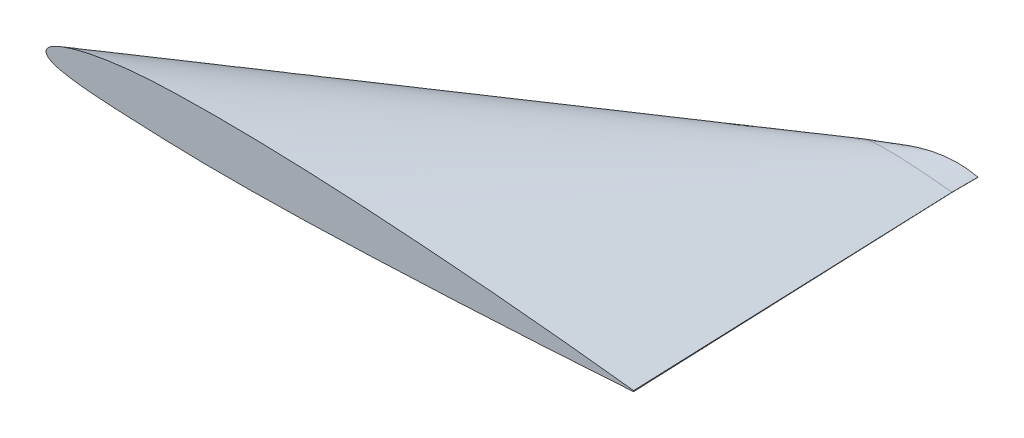
SolidWorks part; units mm, degrees
ref_plane "Plan de face" through (0, 0, 0) normal (0, 0, 1) x (1, 0, 0)
ref_plane "Plan de dessus" through (0, 0, 0) normal (0, 1, 0) x (1, 0, 0)
ref_plane "Plan de droite" through (0, 0, 0) normal (1, 0, 0) x (0, 0, -1)
curve "Courbe1"
  spline degree 3 poles (1018.0214, 0.8551, 0) (1017.4995, 0.9169, 0) (1015.4153, 1.1635, 0) (1010.7382, 1.7165, 0) (1002.9747, 2.6279, 0) (992.1722, 3.8816, 0) (978.3961, 5.4547, 0) (961.7307, 7.3239, 0) (942.2774, 9.4592, 0) (920.1552, 11.8271, 0) (895.4991, 14.3917, 0) (868.4602, 17.118, 0) (839.2041, 19.9687, 0) (807.9105, 22.9034, 0) (774.7711, 25.8837, 0) (739.9899, 28.8733, 0) (703.7802, 31.83, 0) (666.3653, 34.7159, 0) (627.9753, 37.4876, 0) (588.8466, 40.1073, 0) (549.2206, 42.5324, 0) (509.3421, 44.7223, 0) (469.4571, 46.6336, 0) (429.8121, 48.2309, 0) (390.6523, 49.4751, 0) (352.2202, 50.3347, 0) (314.754, 50.7806, 0) (278.4854, 50.792, 0) (243.6395, 50.3489, 0) (210.2839, 49.4637, 0) (178.6046, 48.0469, 0) (148.8474, 45.6903, 0) (121.3708, 42.6096, 0) (96.3889, 38.903, 0) (74.057, 34.7027, 0) (54.5094, 30.1347, 0) (37.8533, 25.3237, 0) (24.1753, 20.3842, 0) (13.4966, 15.4299, 0) (5.8515, 10.4906, 0) (0.9704, 5.571, 0) (-0.6493, -0.0648, 0) (2.0456, -5.2599, 0) (7.7408, -9.1365, 0) (16.0826, -12.5545, 0) (27.3008, -15.5285, 0) (41.3409, -18.1297, 0) (58.1495, -20.3675, 0) (77.6199, -22.2824, 0) (99.6342, -23.9255, 0) (124.0585, -25.3476, 0) (150.7475, -26.6259, 0) (179.5838, -27.8076, 0) (210.5631, -29.0818, 0) (243.5406, -30.0321, 0) (278.2985, -30.5898, 0) (314.476, -30.7851, 0) (351.8516, -30.6369, 0) (390.1961, -30.1714, 0) (429.2739, -29.4218, 0) (468.8455, -28.4222, 0) (508.668, -27.2083, 0) (548.4968, -25.815, 0) (588.0867, -24.2794, 0) (627.1936, -22.6305, 0) (665.5767, -20.9028, 0) (702.9992, -19.1236, 0) (739.2307, -17.3199, 0) (774.0468, -15.514, 0) (807.2325, -13.7303, 0) (838.582, -11.9881, 0) (867.9013, -10.3078, 0) (895.0089, -8.7106, 0) (919.7362, -7.2128, 0) (941.9306, -5.8374, 0) (961.4532, -4.5978, 0) (978.1828, -3.5146, 0) (992.0153, -2.6055, 0) (1002.8642, -1.879, 0) (1010.6624, -1.354, 0) (1015.3606, -1.033, 0) (1017.4544, -0.8907, 0) (1017.9786, -0.8551, 0) knots 0 0 0 0 0.000766 0.003061 0.006869 0.012167 0.018922 0.027092 0.036626 0.047465 0.059542 0.072781 0.087102 0.102414 0.118624 0.135631 0.15333 0.171611 0.190362 0.209467 0.228808 0.248265 0.267718 0.287047 0.306134 0.324861 0.343113 0.360781 0.377757 0.393939 0.409446 0.424002 0.437467 0.449765 0.460829 0.4706 0.479033 0.486099 0.491795 0.49616 0.499335 0.50173 0.504125 0.507289 0.511617 0.517238 0.524181 0.532434 0.541962 0.552713 0.564629 0.577644 0.591683 0.606723 0.622865 0.639799 0.657423 0.67563 0.694311 0.713352 0.732636 0.752045 0.77146 0.790762 0.80983 0.828548 0.8468 0.864473 0.881458 0.897648 0.912944 0.927252 0.940481 0.952549 0.963383 0.972913 0.981081 0.987834 0.993132 0.996939 0.999234 1 1 1 1
sketch "Esquisse1" plane through (0, 0, 0) normal (0, 0, 1) x (1, 0, 0)
  line L0 (1018.0214, 0.8551) -> (1017.9786, -0.8551)
  spline S0 degree 3 poles (2019.3627, 1669.0879) (1545.321, -65.0784) (1279.5358, -30.0658) (1010.7382, 1.7165) (1002.9747, 2.6279) (992.1722, 3.8816) (978.3961, 5.4547) (961.7307, 7.3239) (942.2774, 9.4592) (920.1552, 11.8271) (895.4991, 14.3917) (868.4602, 17.118) (839.2041, 19.9687) (807.9105, 22.9034) (774.7711, 25.8837) (739.9899, 28.8733) (703.7802, 31.83) (666.3653, 34.7159) (627.9753, 37.4876) (588.8466, 40.1073) (549.2206, 42.5324) (509.3421, 44.7223) (469.4571, 46.6336) (429.8121, 48.2309) (390.6523, 49.4751) (352.2202, 50.3347) (314.754, 50.7806) (278.4854, 50.792) (243.6395, 50.3489) (210.2839, 49.4637) (178.6046, 48.0469) (148.8474, 45.6903) (121.3708, 42.6096) (96.3889, 38.903) (74.057, 34.7027) (54.5094, 30.1347) (37.8533, 25.3237) (24.1753, 20.3842) (13.4966, 15.4299) (5.8515, 10.4906) (0.9704, 5.571) (-0.6493, -0.0648) (2.0456, -5.2599) (7.7408, -9.1365) (16.0826, -12.5545) (27.3008, -15.5285) (41.3409, -18.1297) (58.1495, -20.3675) (77.6199, -22.2824) (99.6342, -23.9255) (124.0585, -25.3476) (150.7475, -26.6259) (179.5838, -27.8076) (210.5631, -29.0818) (243.5406, -30.0321) (278.2985, -30.5898) (314.476, -30.7851) (351.8516, -30.6369) (390.1961, -30.1714) (429.2739, -29.4218) (468.8455, -28.4222) (508.668, -27.2083) (548.4968, -25.815) (588.0867, -24.2794) (627.1936, -22.6305) (665.5767, -20.9028) (702.9992, -19.1236) (739.2307, -17.3199) (774.0468, -15.514) (807.2325, -13.7303) (838.582, -11.9881) (867.9013, -10.3078) (895.0089, -8.7106) (919.7362, -7.2128) (941.9306, -5.8374) (961.4532, -4.5978) (978.1828, -3.5146) (992.0153, -2.6055) (1002.8642, -1.879) (1010.6624, -1.354) (1187.4361, 10.7265) (1362.009, 16.688) (1404.8675, 1937.5859) knots -0.387905 -0.387905 -0.387905 -0.387905 0.000766 0.003061 0.006869 0.012167 0.018922 0.027092 0.036626 0.047465 0.059542 0.072781 0.087102 0.102414 0.118624 0.135631 0.15333 0.171611 0.190362 0.209467 0.228808 0.248265 0.267718 0.287047 0.306134 0.324861 0.343113 0.360781 0.377757 0.393939 0.409446 0.424002 0.437467 0.449765 0.460829 0.4706 0.479033 0.486099 0.491795 0.49616 0.499335 0.50173 0.504125 0.507289 0.511617 0.517238 0.524181 0.532434 0.541962 0.552713 0.564629 0.577644 0.591683 0.606723 0.622865 0.639799 0.657423 0.67563 0.694311 0.713352 0.732636 0.752045 0.77146 0.790762 0.80983 0.828548 0.8468 0.864473 0.881458 0.897648 0.912944 0.927252 0.940481 0.952549 0.963383 0.972913 0.981081 0.987834 0.993132 0.996939 0.999234 1.251559 1.251559 1.251559 1.251559 only from (1018.0214, 0.8551) to (1017.9786, -0.8551) construction
  spline S1 degree 3 poles (1018.0214, 0.8551) (1015.9372, 1.1018) (1011.2602, 1.6553) (1002.9747, 2.6279) (992.1722, 3.8816) (978.3961, 5.4547) (961.7307, 7.3239) (942.2774, 9.4592) (920.1552, 11.8271) (895.4991, 14.3917) (868.4602, 17.118) (839.2041, 19.9687) (807.9105, 22.9034) (774.7711, 25.8837) (739.9899, 28.8733) (703.7802, 31.83) (666.3653, 34.7159) (627.9753, 37.4876) (588.8466, 40.1073) (549.2206, 42.5324) (509.3421, 44.7223) (469.4571, 46.6336) (429.8121, 48.2309) (390.6523, 49.4751) (352.2202, 50.3347) (314.754, 50.7806) (278.4854, 50.792) (243.6395, 50.3489) (210.2839, 49.4637) (178.6046, 48.0469) (148.8474, 45.6903) (121.3708, 42.6096) (96.3889, 38.903) (74.057, 34.7027) (54.5094, 30.1347) (37.8533, 25.3237) (24.1753, 20.3842) (13.4966, 15.4299) (5.8515, 10.4906) (0.9704, 5.571) (-0.6493, -0.0648) (2.0456, -5.2599) (7.7408, -9.1365) (16.0826, -12.5545) (27.3008, -15.5285) (41.3409, -18.1297) (58.1495, -20.3675) (77.6199, -22.2824) (99.6342, -23.9255) (124.0585, -25.3476) (150.7475, -26.6259) (179.5838, -27.8076) (210.5631, -29.0818) (243.5406, -30.0321) (278.2985, -30.5898) (314.476, -30.7851) (351.8516, -30.6369) (390.1961, -30.1714) (429.2739, -29.4218) (468.8455, -28.4222) (508.668, -27.2083) (548.4968, -25.815) (588.0867, -24.2794) (627.1936, -22.6305) (665.5767, -20.9028) (702.9992, -19.1236) (739.2307, -17.3199) (774.0468, -15.514) (807.2325, -13.7303) (838.582, -11.9881) (867.9013, -10.3078) (895.0089, -8.7106) (919.7362, -7.2128) (941.9306, -5.8374) (961.4532, -4.5978) (978.1828, -3.5146) (992.0153, -2.6055) (1002.8642, -1.879) (1010.6624, -1.354) (1015.3606, -1.033) (1017.4544, -0.8907) (1017.9786, -0.8551) knots 0 0 0 0 0.003061 0.006869 0.012167 0.018922 0.027092 0.036626 0.047465 0.059542 0.072781 0.087102 0.102414 0.118624 0.135631 0.15333 0.171611 0.190362 0.209467 0.228808 0.248265 0.267718 0.287047 0.306134 0.324861 0.343113 0.360781 0.377757 0.393939 0.409446 0.424002 0.437467 0.449765 0.460829 0.4706 0.479033 0.486099 0.491795 0.49616 0.499335 0.50173 0.504125 0.507289 0.511617 0.517238 0.524181 0.532434 0.541962 0.552713 0.564629 0.577644 0.591683 0.606723 0.622865 0.639799 0.657423 0.67563 0.694311 0.713352 0.732636 0.752045 0.77146 0.790762 0.80983 0.828548 0.8468 0.864473 0.881458 0.897648 0.912944 0.927252 0.940481 0.952549 0.963383 0.972913 0.981081 0.987834 0.993132 0.996939 0.999234 1 1 1 1
ref_plane "Plan1" through (0, 0, 3692) normal (0, 0, 1) x (1, 0, 0)
curve "Courbe6"
  spline degree 3 poles (1163.1375, 5.4995, 3692) (1159.7811, 5.8967, 3692) (1146.3774, 7.4829, 3692) (1116.2978, 11.0395, 3692) (1066.3687, 16.9004, 3692) (996.8956, 24.9635, 3692) (908.2981, 35.0805, 3692) (801.1189, 47.1015, 3692) (676.0101, 60.8344, 3692) (533.737, 76.0629, 3692) (375.1675, 92.5562, 3692) (201.2738, 110.0899, 3692) (13.1209, 128.4236, 3692) (-188.1357, 147.2973, 3692) (-401.2627, 166.4645, 3692) (-624.9492, 185.6913, 3692) (-857.8221, 204.7062, 3692) (-1098.4462, 223.2663, 3692) (-1345.3414, 241.0915, 3692) (-1596.9874, 257.9399, 3692) (-1851.8314, 273.5362, 3692) (-2108.3, 287.6194, 3692) (-2364.8099, 299.9116, 3692) (-2619.7762, 310.1846, 3692) (-2871.6223, 318.1858, 3692) (-3118.7881, 323.7144, 3692) (-3359.7421, 326.5819, 3692) (-3592.9943, 326.6555, 3692) (-3817.0964, 323.8061, 3692) (-4031.6141, 318.1125, 3692) (-4235.3513, 309.001, 3692) (-4426.7271, 293.8451, 3692) (-4603.4357, 274.0325, 3692) (-4764.1004, 250.1942, 3692) (-4907.7217, 223.1815, 3692) (-5033.4374, 193.8031, 3692) (-5140.5567, 162.863, 3692) (-5228.523, 131.0958, 3692) (-5297.1999, 99.2336, 3692) (-5346.3678, 67.4673, 3692) (-5377.759, 35.8287, 3692) (-5388.1761, -0.4169, 3692) (-5370.8441, -33.8274, 3692) (-5334.217, -58.7592, 3692) (-5280.5689, -80.741, 3692) (-5208.4223, -99.8674, 3692) (-5118.1271, -116.5961, 3692) (-5010.0265, -130.9881, 3692) (-4884.8083, -143.3033, 3692) (-4743.2287, -153.8705, 3692) (-4586.1505, -163.0167, 3692) (-4414.5067, -171.2373, 3692) (-4229.054, -178.8373, 3692) (-4029.8189, -187.0319, 3692) (-3817.7327, -193.1434, 3692) (-3594.1965, -196.7305, 3692) (-3361.5299, -197.9864, 3692) (-3121.1589, -197.0334, 3692) (-2874.556, -194.0395, 3692) (-2623.2373, -189.2185, 3692) (-2368.743, -182.7897, 3692) (-2112.6351, -174.9833, 3692) (-1856.4867, -166.0227, 3692) (-1601.8747, -156.1465, 3692) (-1350.369, -145.5422, 3692) (-1103.5178, -134.4311, 3692) (-862.8449, -122.9884, 3692) (-629.8315, -111.3885, 3692) (-405.9209, -99.7741, 3692) (-192.4958, -88.3026, 3692) (9.1204, -77.0986, 3692) (197.6796, -66.2922, 3692) (372.0148, -56.0201, 3692) (531.0422, -46.3873, 3692) (673.7795, -37.5414, 3692) (799.3341, -29.5694, 3692) (906.9261, -22.6031, 3692) (995.8864, -16.7568, 3692) (1065.6581, -12.0843, 3692) (1115.8103, -8.708, 3692) (1146.0257, -6.6432, 3692) (1159.4908, -5.7285, 3692) (1162.8625, -5.4995, 3692) knots 0 0 0 0 0.000766 0.003061 0.006869 0.012167 0.018922 0.027092 0.036626 0.047465 0.059542 0.072781 0.087102 0.102414 0.118624 0.135631 0.15333 0.171611 0.190362 0.209467 0.228808 0.248265 0.267718 0.287047 0.306134 0.324861 0.343113 0.360781 0.377757 0.393939 0.409446 0.424002 0.437467 0.449765 0.460829 0.4706 0.479033 0.486099 0.491795 0.49616 0.499335 0.50173 0.504125 0.507289 0.511617 0.517238 0.524181 0.532434 0.541962 0.552713 0.564629 0.577644 0.591683 0.606723 0.622865 0.639799 0.657423 0.67563 0.694311 0.713352 0.732636 0.752045 0.77146 0.790762 0.80983 0.828548 0.8468 0.864473 0.881458 0.897648 0.912944 0.927252 0.940481 0.952549 0.963383 0.972913 0.981081 0.987834 0.993132 0.996939 0.999234 1 1 1 1
sketch "Esquisse4" plane through (0, 0, 3692) normal (0, 0, 1) x (1, 0, 0)
  line L0 (1163.1375, 5.4995) -> (1162.8625, -5.4995)
  spline S0 degree 3 poles (3092.3515, 339.1342) (2401.749, -144.1196) (1767.5466, -65.9634) (1116.2978, 11.0395) (1066.3687, 16.9004) (996.8956, 24.9635) (908.2981, 35.0805) (801.1189, 47.1015) (676.0101, 60.8344) (533.737, 76.0629) (375.1675, 92.5562) (201.2738, 110.0899) (13.1209, 128.4236) (-188.1357, 147.2973) (-401.2627, 166.4645) (-624.9492, 185.6913) (-857.8221, 204.7062) (-1098.4462, 223.2663) (-1345.3414, 241.0915) (-1596.9874, 257.9399) (-1851.8314, 273.5362) (-2108.3, 287.6194) (-2364.8099, 299.9116) (-2619.7762, 310.1846) (-2871.6223, 318.1858) (-3118.7881, 323.7144) (-3359.7421, 326.5819) (-3592.9943, 326.6555) (-3817.0964, 323.8061) (-4031.6141, 318.1125) (-4235.3513, 309.001) (-4426.7271, 293.8451) (-4603.4357, 274.0325) (-4764.1004, 250.1942) (-4907.7217, 223.1815) (-5033.4374, 193.8031) (-5140.5567, 162.863) (-5228.523, 131.0958) (-5297.1999, 99.2336) (-5346.3678, 67.4673) (-5377.759, 35.8287) (-5388.1761, -0.4169) (-5370.8441, -33.8274) (-5334.217, -58.7592) (-5280.5689, -80.741) (-5208.4223, -99.8674) (-5118.1271, -116.5961) (-5010.0265, -130.9881) (-4884.8083, -143.3033) (-4743.2287, -153.8705) (-4586.1505, -163.0167) (-4414.5067, -171.2373) (-4229.054, -178.8373) (-4029.8189, -187.0319) (-3817.7327, -193.1434) (-3594.1965, -196.7305) (-3361.5299, -197.9864) (-3121.1589, -197.0334) (-2874.556, -194.0395) (-2623.2373, -189.2185) (-2368.743, -182.7897) (-2112.6351, -174.9833) (-1856.4867, -166.0227) (-1601.8747, -156.1465) (-1350.369, -145.5422) (-1103.5178, -134.4311) (-862.8449, -122.9884) (-629.8315, -111.3885) (-405.9209, -99.7741) (-192.4958, -88.3026) (9.1204, -77.0986) (197.6796, -66.2922) (372.0148, -56.0201) (531.0422, -46.3873) (673.7795, -37.5414) (799.3341, -29.5694) (906.9261, -22.6031) (995.8864, -16.7568) (1065.6581, -12.0843) (1115.8103, -8.708) (1645.6756, 27.5023) (2159.3351, 54.5502) (2585.29, 1222.9368) knots -0.141853 -0.141853 -0.141853 -0.141853 0.000766 0.003061 0.006869 0.012167 0.018922 0.027092 0.036626 0.047465 0.059542 0.072781 0.087102 0.102414 0.118624 0.135631 0.15333 0.171611 0.190362 0.209467 0.228808 0.248265 0.267718 0.287047 0.306134 0.324861 0.343113 0.360781 0.377757 0.393939 0.409446 0.424002 0.437467 0.449765 0.460829 0.4706 0.479033 0.486099 0.491795 0.49616 0.499335 0.50173 0.504125 0.507289 0.511617 0.517238 0.524181 0.532434 0.541962 0.552713 0.564629 0.577644 0.591683 0.606723 0.622865 0.639799 0.657423 0.67563 0.694311 0.713352 0.732636 0.752045 0.77146 0.790762 0.80983 0.828548 0.8468 0.864473 0.881458 0.897648 0.912944 0.927252 0.940481 0.952549 0.963383 0.972913 0.981081 0.987834 0.993132 0.996939 0.999234 1.113577 1.113577 1.113577 1.113577 only from (1163.1375, 5.4995) to (1162.8625, -5.4995) construction
  spline S1 degree 3 poles (1163.1375, 5.4995) (1159.7811, 5.8967) (1146.3774, 7.4829) (1116.2978, 11.0395) (1066.3687, 16.9004) (996.8956, 24.9635) (908.2981, 35.0805) (801.1189, 47.1015) (676.0101, 60.8344) (533.737, 76.0629) (375.1675, 92.5562) (201.2738, 110.0899) (13.1209, 128.4236) (-188.1357, 147.2973) (-401.2627, 166.4645) (-624.9492, 185.6913) (-857.8221, 204.7062) (-1098.4462, 223.2663) (-1345.3414, 241.0915) (-1596.9874, 257.9399) (-1851.8314, 273.5362) (-2108.3, 287.6194) (-2364.8099, 299.9116) (-2619.7762, 310.1846) (-2871.6223, 318.1858) (-3118.7881, 323.7144) (-3359.7421, 326.5819) (-3592.9943, 326.6555) (-3817.0964, 323.8061) (-4031.6141, 318.1125) (-4235.3513, 309.001) (-4426.7271, 293.8451) (-4603.4357, 274.0325) (-4764.1004, 250.1942) (-4907.7217, 223.1815) (-5033.4374, 193.8031) (-5140.5567, 162.863) (-5228.523, 131.0958) (-5297.1999, 99.2336) (-5346.3678, 67.4673) (-5377.759, 35.8287) (-5388.1761, -0.4169) (-5370.8441, -33.8274) (-5334.217, -58.7592) (-5280.5689, -80.741) (-5208.4223, -99.8674) (-5118.1271, -116.5961) (-5010.0265, -130.9881) (-4884.8083, -143.3033) (-4743.2287, -153.8705) (-4586.1505, -163.0167) (-4414.5067, -171.2373) (-4229.054, -178.8373) (-4029.8189, -187.0319) (-3817.7327, -193.1434) (-3594.1965, -196.7305) (-3361.5299, -197.9864) (-3121.1589, -197.0334) (-2874.556, -194.0395) (-2623.2373, -189.2185) (-2368.743, -182.7897) (-2112.6351, -174.9833) (-1856.4867, -166.0227) (-1601.8747, -156.1465) (-1350.369, -145.5422) (-1103.5178, -134.4311) (-862.8449, -122.9884) (-629.8315, -111.3885) (-405.9209, -99.7741) (-192.4958, -88.3026) (9.1204, -77.0986) (197.6796, -66.2922) (372.0148, -56.0201) (531.0422, -46.3873) (673.7795, -37.5414) (799.3341, -29.5694) (906.9261, -22.6031) (995.8864, -16.7568) (1065.6581, -12.0843) (1115.8103, -8.708) (1146.0257, -6.6432) (1159.4908, -5.7285) (1162.8625, -5.4995) knots 0 0 0 0 0.000766 0.003061 0.006869 0.012167 0.018922 0.027092 0.036626 0.047465 0.059542 0.072781 0.087102 0.102414 0.118624 0.135631 0.15333 0.171611 0.190362 0.209467 0.228808 0.248265 0.267718 0.287047 0.306134 0.324861 0.343113 0.360781 0.377757 0.393939 0.409446 0.424002 0.437467 0.449765 0.460829 0.4706 0.479033 0.486099 0.491795 0.49616 0.499335 0.50173 0.504125 0.507289 0.511617 0.517238 0.524181 0.532434 0.541962 0.552713 0.564629 0.577644 0.591683 0.606723 0.622865 0.639799 0.657423 0.67563 0.694311 0.713352 0.732636 0.752045 0.77146 0.790762 0.80983 0.828548 0.8468 0.864473 0.881458 0.897648 0.912944 0.927252 0.940481 0.952549 0.963383 0.972913 0.981081 0.987834 0.993132 0.996939 0.999234 1 1 1 1
loft "Lissage2" add profiles "Esquisse4", "Esquisse1" connector at (1163.1375, 5.4995, 3692) connector at (1018.0214, 0.8551, 0)
ref_plane "Plan4" through (0, 0, 0) normal (0, 1, 0) x (1, 0, 0)
ref_plane "Plan5" through (0, 0, -291) normal (0, 0, 1) x (1, 0, 0)
ref_plane "Plan6" through (0, 0, 0) normal (0, 0, 1) x (1, 0, 0)
sketch "Esquisse10" plane through (0, 0, 0) normal (0, 0, 1) x (1, 0, 0)
  line L0 (1018.0214, 0.8551) -> (1017.9786, -0.8551)
  spline S0 degree 3 poles (2019.3627, 1669.0879) (1545.321, -65.0784) (1279.5358, -30.0658) (1010.7382, 1.7165) (1002.9747, 2.6279) (992.1722, 3.8816) (978.3961, 5.4547) (961.7307, 7.3239) (942.2774, 9.4592) (920.1552, 11.8271) (895.4991, 14.3917) (868.4602, 17.118) (839.2041, 19.9687) (807.9105, 22.9034) (774.7711, 25.8837) (739.9899, 28.8733) (703.7802, 31.83) (666.3653, 34.7159) (627.9753, 37.4876) (588.8466, 40.1073) (549.2206, 42.5324) (509.3421, 44.7223) (469.4571, 46.6336) (429.8121, 48.2309) (390.6523, 49.4751) (352.2202, 50.3347) (314.754, 50.7806) (278.4854, 50.792) (243.6395, 50.3489) (210.2839, 49.4637) (178.6046, 48.0469) (148.8474, 45.6903) (121.3708, 42.6096) (96.3889, 38.903) (74.057, 34.7027) (54.5094, 30.1347) (37.8533, 25.3237) (24.1753, 20.3842) (13.4966, 15.4299) (5.8515, 10.4906) (0.9704, 5.571) (-0.6493, -0.0648) (2.0456, -5.2599) (7.7408, -9.1365) (16.0826, -12.5545) (27.3008, -15.5285) (41.3409, -18.1297) (58.1495, -20.3675) (77.6199, -22.2824) (99.6342, -23.9255) (124.0585, -25.3476) (150.7475, -26.6259) (179.5838, -27.8076) (210.5631, -29.0818) (243.5406, -30.0321) (278.2985, -30.5898) (314.476, -30.7851) (351.8516, -30.6369) (390.1961, -30.1714) (429.2739, -29.4218) (468.8455, -28.4222) (508.668, -27.2083) (548.4968, -25.815) (588.0867, -24.2794) (627.1936, -22.6305) (665.5767, -20.9028) (702.9992, -19.1236) (739.2307, -17.3199) (774.0468, -15.514) (807.2325, -13.7303) (838.582, -11.9881) (867.9013, -10.3078) (895.0089, -8.7106) (919.7362, -7.2128) (941.9306, -5.8374) (961.4532, -4.5978) (978.1828, -3.5146) (992.0153, -2.6055) (1002.8642, -1.879) (1010.6624, -1.354) (1187.4361, 10.7265) (1362.009, 16.688) (1404.8675, 1937.5859) knots -0.387905 -0.387905 -0.387905 -0.387905 0.000766 0.003061 0.006869 0.012167 0.018922 0.027092 0.036626 0.047465 0.059542 0.072781 0.087102 0.102414 0.118624 0.135631 0.15333 0.171611 0.190362 0.209467 0.228808 0.248265 0.267718 0.287047 0.306134 0.324861 0.343113 0.360781 0.377757 0.393939 0.409446 0.424002 0.437467 0.449765 0.460829 0.4706 0.479033 0.486099 0.491795 0.49616 0.499335 0.50173 0.504125 0.507289 0.511617 0.517238 0.524181 0.532434 0.541962 0.552713 0.564629 0.577644 0.591683 0.606723 0.622865 0.639799 0.657423 0.67563 0.694311 0.713352 0.732636 0.752045 0.77146 0.790762 0.80983 0.828548 0.8468 0.864473 0.881458 0.897648 0.912944 0.927252 0.940481 0.952549 0.963383 0.972913 0.981081 0.987834 0.993132 0.996939 0.999234 1.251559 1.251559 1.251559 1.251559 only from (1018.0214, 0.8551) to (1017.9786, -0.8551) construction
  spline S1 degree 3 poles (1018.0214, 0.8551) (1015.9372, 1.1018) (1011.2602, 1.6553) (1002.9747, 2.6279) (992.1722, 3.8816) (978.3961, 5.4547) (961.7307, 7.3239) (942.2774, 9.4592) (920.1552, 11.8271) (895.4991, 14.3917) (868.4602, 17.118) (839.2041, 19.9687) (807.9105, 22.9034) (774.7711, 25.8837) (739.9899, 28.8733) (703.7802, 31.83) (666.3653, 34.7159) (627.9753, 37.4876) (588.8466, 40.1073) (549.2206, 42.5324) (509.3421, 44.7223) (469.4571, 46.6336) (429.8121, 48.2309) (390.6523, 49.4751) (352.2202, 50.3347) (314.754, 50.7806) (278.4854, 50.792) (243.6395, 50.3489) (210.2839, 49.4637) (178.6046, 48.0469) (148.8474, 45.6903) (121.3708, 42.6096) (96.3889, 38.903) (74.057, 34.7027) (54.5094, 30.1347) (37.8533, 25.3237) (24.1753, 20.3842) (13.4966, 15.4299) (5.8515, 10.4906) (0.9704, 5.571) (-0.6493, -0.0648) (2.0456, -5.2599) (7.7408, -9.1365) (16.0826, -12.5545) (27.3008, -15.5285) (41.3409, -18.1297) (58.1495, -20.3675) (77.6199, -22.2824) (99.6342, -23.9255) (124.0585, -25.3476) (150.7475, -26.6259) (179.5838, -27.8076) (210.5631, -29.0818) (243.5406, -30.0321) (278.2985, -30.5898) (314.476, -30.7851) (351.8516, -30.6369) (390.1961, -30.1714) (429.2739, -29.4218) (468.8455, -28.4222) (508.668, -27.2083) (548.4968, -25.815) (588.0867, -24.2794) (627.1936, -22.6305) (665.5767, -20.9028) (702.9992, -19.1236) (739.2307, -17.3199) (774.0468, -15.514) (807.2325, -13.7303) (838.582, -11.9881) (867.9013, -10.3078) (895.0089, -8.7106) (919.7362, -7.2128) (941.9306, -5.8374) (961.4532, -4.5978) (978.1828, -3.5146) (992.0153, -2.6055) (1002.8642, -1.879) (1010.6624, -1.354) (1015.3606, -1.033) (1017.4544, -0.8907) (1017.9786, -0.8551) knots 0 0 0 0 0.003061 0.006869 0.012167 0.018922 0.027092 0.036626 0.047465 0.059542 0.072781 0.087102 0.102414 0.118624 0.135631 0.15333 0.171611 0.190362 0.209467 0.228808 0.248265 0.267718 0.287047 0.306134 0.324861 0.343113 0.360781 0.377757 0.393939 0.409446 0.424002 0.437467 0.449765 0.460829 0.4706 0.479033 0.486099 0.491795 0.49616 0.499335 0.50173 0.504125 0.507289 0.511617 0.517238 0.524181 0.532434 0.541962 0.552713 0.564629 0.577644 0.591683 0.606723 0.622865 0.639799 0.657423 0.67563 0.694311 0.713352 0.732636 0.752045 0.77146 0.790762 0.80983 0.828548 0.8468 0.864473 0.881458 0.897648 0.912944 0.927252 0.940481 0.952549 0.963383 0.972913 0.981081 0.987834 0.993132 0.996939 0.999234 1 1 1 1
curve "Courbe10"
  spline degree 3 poles (1017.0107, 0.8551, -291) (1016.7497, 0.9169, -291) (1015.7077, 1.1635, -291) (1013.3695, 1.7164, -291) (1009.4884, 2.6276, -291) (1004.088, 3.8812, -291) (997.2006, 5.4541, -291) (988.8688, 7.3231, -291) (979.1431, 9.4583, -291) (968.0829, 11.826, -291) (955.7556, 14.3904, -291) (942.2369, 17.1166, -291) (927.6096, 19.9673, -291) (911.9634, 22.9019, -291) (895.3942, 25.8822, -291) (878.0042, 28.8718, -291) (859.8998, 31.8284, -291) (841.1929, 34.7144, -291) (821.9981, 37.4861, -291) (802.434, 40.106, -291) (782.6211, 42.5312, -291) (762.6817, 44.7212, -291) (742.7385, 46.6327, -291) (722.9151, 48.2303, -291) (703.3336, 49.4747, -291) (684.1152, 50.3345, -291) (665.379, 50.7806, -291) (647.2406, 50.792, -291) (629.8125, 50.3486, -291) (613.1253, 49.4628, -291) (597.2564, 48.0417, -291) (582.3575, 45.678, -291) (568.5995, 42.5877, -291) (556.0896, 38.8683, -291) (544.9041, 34.6511, -291) (535.1075, 30.0596, -291) (526.753, 25.2127, -291) (519.8773, 20.2199, -291) (514.5062, 15.1662, -291) (510.6558, 10.1076, -291) (508.3568, 5.0526, -291) (507.7205, 0.0681, -291) (508.7706, -4.6534, -291) (511.5382, -8.8391, -291) (515.8156, -12.4077, -291) (521.505, -15.4711, -291) (528.5835, -18.1028, -291) (537.0219, -20.3563, -291) (546.7785, -22.2771, -291) (557.7983, -23.9231, -291) (570.0185, -25.3465, -291) (583.3678, -26.6254, -291) (597.79, -27.8074, -291) (613.2723, -29.0811, -291) (629.7632, -30.0318, -291) (647.1462, -30.5898, -291) (665.2378, -30.7851, -291) (683.9277, -30.6369, -291) (703.1013, -30.1713, -291) (722.641, -29.4216, -291) (742.4271, -28.4219, -291) (762.3384, -27.2081, -291) (782.2526, -25.8147, -291) (802.0473, -24.2791, -291) (821.6004, -22.6302, -291) (840.7917, -20.9025, -291) (859.5026, -19.1233, -291) (877.6182, -17.3196, -291) (895.0259, -15.5137, -291) (911.6186, -13.73, -291) (927.2932, -11.9879, -291) (941.9526, -10.3076, -291) (955.5063, -8.7104, -291) (967.8696, -7.2126, -291) (978.9667, -5.8372, -291) (988.7277, -4.5976, -291) (997.0922, -3.5145, -291) (1004.0083, -2.6055, -291) (1009.4323, -1.879, -291) (1013.3315, -1.354, -291) (1015.6803, -1.033, -291) (1016.7272, -0.8907, -291) (1016.9893, -0.8551, -291) knots 0 0 0 0 0.000765 0.003056 0.006858 0.012145 0.018881 0.027023 0.036517 0.047302 0.059307 0.072456 0.086665 0.101843 0.117894 0.134717 0.152207 0.170253 0.188743 0.207562 0.226592 0.245716 0.264816 0.283775 0.302479 0.320817 0.338681 0.355969 0.372585 0.388436 0.403662 0.418038 0.431461 0.443882 0.455259 0.46555 0.474729 0.482787 0.489753 0.495708 0.500826 0.505425 0.509803 0.514334 0.519483 0.52555 0.532697 0.540993 0.550455 0.561066 0.572788 0.585567 0.599341 0.614091 0.629907 0.646483 0.663729 0.681545 0.699829 0.71847 0.737357 0.756375 0.775408 0.794337 0.813045 0.831416 0.849336 0.866693 0.883379 0.89929 0.914326 0.928394 0.941406 0.95328 0.963941 0.973323 0.981364 0.988015 0.993233 0.996984 0.999245 1 1 1 1
sketch "Esquisse11" plane through (0, 0, -291) normal (0, 0, 1) x (1, 0, 0)
  line L0 (1017.0107, 0.8551) -> (1016.9893, -0.8551)
  spline S0 degree 3 poles (1875.4118, 1790.1687) (1289.8127, -67.5103) (1152.672, -31.2255) (1013.3695, 1.7164) (1009.4884, 2.6276) (1004.088, 3.8812) (997.2006, 5.4541) (988.8688, 7.3231) (979.1431, 9.4583) (968.0829, 11.826) (955.7556, 14.3904) (942.2369, 17.1166) (927.6096, 19.9673) (911.9634, 22.9019) (895.3942, 25.8822) (878.0042, 28.8718) (859.8998, 31.8284) (841.1929, 34.7144) (821.9981, 37.4861) (802.434, 40.106) (782.6211, 42.5312) (762.6817, 44.7212) (742.7385, 46.6327) (722.9151, 48.2303) (703.3336, 49.4747) (684.1152, 50.3345) (665.379, 50.7806) (647.2406, 50.792) (629.8125, 50.3486) (613.1253, 49.4628) (597.2564, 48.0417) (582.3575, 45.678) (568.5995, 42.5877) (556.0896, 38.8683) (544.9041, 34.6511) (535.1075, 30.0596) (526.753, 25.2127) (519.8773, 20.2199) (514.5062, 15.1662) (510.6558, 10.1076) (508.3568, 5.0526) (507.7205, 0.0681) (508.7706, -4.6534) (511.5382, -8.8391) (515.8156, -12.4077) (521.505, -15.4711) (528.5835, -18.1028) (537.0219, -20.3563) (546.7785, -22.2771) (557.7983, -23.9231) (570.0185, -25.3465) (583.3678, -26.6254) (597.79, -27.8074) (613.2723, -29.0811) (629.7632, -30.0318) (647.1462, -30.5898) (665.2378, -30.7851) (683.9277, -30.6369) (703.1013, -30.1713) (722.641, -29.4216) (742.4271, -28.4219) (762.3384, -27.2081) (782.2526, -25.8147) (802.0473, -24.2791) (821.6004, -22.6302) (840.7917, -20.9025) (859.5026, -19.1233) (877.6182, -17.3196) (895.0259, -15.5137) (911.6186, -13.73) (927.2932, -11.9879) (941.9526, -10.3076) (955.5063, -8.7104) (967.8696, -7.2126) (978.9667, -5.8372) (988.7277, -4.5976) (997.0922, -3.5145) (1004.0083, -2.6055) (1009.4323, -1.879) (1013.3315, -1.354) (1102.9272, 10.8917) (1192.0398, 16.9345) (1012.599, 1992.937) knots -0.401721 -0.401721 -0.401721 -0.401721 0.000765 0.003056 0.006858 0.012145 0.018881 0.027023 0.036517 0.047302 0.059307 0.072456 0.086665 0.101843 0.117894 0.134717 0.152207 0.170253 0.188743 0.207562 0.226592 0.245716 0.264816 0.283775 0.302479 0.320817 0.338681 0.355969 0.372585 0.388436 0.403662 0.418038 0.431461 0.443882 0.455259 0.46555 0.474729 0.482787 0.489753 0.495708 0.500826 0.505425 0.509803 0.514334 0.519483 0.52555 0.532697 0.540993 0.550455 0.561066 0.572788 0.585567 0.599341 0.614091 0.629907 0.646483 0.663729 0.681545 0.699829 0.71847 0.737357 0.756375 0.775408 0.794337 0.813045 0.831416 0.849336 0.866693 0.883379 0.89929 0.914326 0.928394 0.941406 0.95328 0.963941 0.973323 0.981364 0.988015 0.993233 0.996984 0.999245 1.251345 1.251345 1.251345 1.251345 only from (1017.0107, 0.8551) to (1016.9893, -0.8551) construction
  spline S1 degree 3 poles (1017.0107, 0.8551) (1015.9687, 1.1018) (1013.6306, 1.6552) (1009.4884, 2.6276) (1004.088, 3.8812) (997.2006, 5.4541) (988.8688, 7.3231) (979.1431, 9.4583) (968.0829, 11.826) (955.7556, 14.3904) (942.2369, 17.1166) (927.6096, 19.9673) (911.9634, 22.9019) (895.3942, 25.8822) (878.0042, 28.8718) (859.8998, 31.8284) (841.1929, 34.7144) (821.9981, 37.4861) (802.434, 40.106) (782.6211, 42.5312) (762.6817, 44.7212) (742.7385, 46.6327) (722.9151, 48.2303) (703.3336, 49.4747) (684.1152, 50.3345) (665.379, 50.7806) (647.2406, 50.792) (629.8125, 50.3486) (613.1253, 49.4628) (597.2564, 48.0417) (582.3575, 45.678) (568.5995, 42.5877) (556.0896, 38.8683) (544.9041, 34.6511) (535.1075, 30.0596) (526.753, 25.2127) (519.8773, 20.2199) (514.5062, 15.1662) (510.6558, 10.1076) (508.3568, 5.0526) (507.7205, 0.0681) (508.7706, -4.6534) (511.5382, -8.8391) (515.8156, -12.4077) (521.505, -15.4711) (528.5835, -18.1028) (537.0219, -20.3563) (546.7785, -22.2771) (557.7983, -23.9231) (570.0185, -25.3465) (583.3678, -26.6254) (597.79, -27.8074) (613.2723, -29.0811) (629.7632, -30.0318) (647.1462, -30.5898) (665.2378, -30.7851) (683.9277, -30.6369) (703.1013, -30.1713) (722.641, -29.4216) (742.4271, -28.4219) (762.3384, -27.2081) (782.2526, -25.8147) (802.0473, -24.2791) (821.6004, -22.6302) (840.7917, -20.9025) (859.5026, -19.1233) (877.6182, -17.3196) (895.0259, -15.5137) (911.6186, -13.73) (927.2932, -11.9879) (941.9526, -10.3076) (955.5063, -8.7104) (967.8696, -7.2126) (978.9667, -5.8372) (988.7277, -4.5976) (997.0922, -3.5145) (1004.0083, -2.6055) (1009.4323, -1.879) (1013.3315, -1.354) (1015.6803, -1.033) (1016.7272, -0.8907) (1016.9893, -0.8551) knots 0 0 0 0 0.003056 0.006858 0.012145 0.018881 0.027023 0.036517 0.047302 0.059307 0.072456 0.086665 0.101843 0.117894 0.134717 0.152207 0.170253 0.188743 0.207562 0.226592 0.245716 0.264816 0.283775 0.302479 0.320817 0.338681 0.355969 0.372585 0.388436 0.403662 0.418038 0.431461 0.443882 0.455259 0.46555 0.474729 0.482787 0.489753 0.495708 0.500826 0.505425 0.509803 0.514334 0.519483 0.52555 0.532697 0.540993 0.550455 0.561066 0.572788 0.585567 0.599341 0.614091 0.629907 0.646483 0.663729 0.681545 0.699829 0.71847 0.737357 0.756375 0.775408 0.794337 0.813045 0.831416 0.849336 0.866693 0.883379 0.89929 0.914326 0.928394 0.941406 0.95328 0.963941 0.973323 0.981364 0.988015 0.993233 0.996984 0.999245 1 1 1 1
loft "Lissage11" add profiles "Esquisse11", "Esquisse10" end constraint default connector at (1017.0107, 0.8551, -291) connector at (1018.0214, 0.8551, 0)
sketch "Esquisse14" plane through (0, 0, 0) normal (0, 1, 0) x (1, 0, 0)
  line L0 (0, 0) -> (1017.0107, 291)
  line L1 (-292.6982, 291) -> (292.6982, 291) construction
  line L2 (1018.0214, 0) -> (1017.0107, 291) construction
  line L3 (1017.0107, 291) -> (1018.0214, 0)
  line L4 (-292.6982, 0) -> (292.6982, 0) construction
  line L5 (1018.0214, 0) -> (0, 0)
  line L6 (508.5053, 145.5) -> (508.5053, 293.6468)
  line L7 (0, 0) -> (508.5053, 293.6468)
  line L8 (508.5053, 293.6468) -> (1017.0107, 291)
  line L9 (1018.0214, 0) -> (1017.0107, 291)
  arc A0 (0, 0) -> (1017.0107, 291) centre (1035.0546, -1694.7277) cw
  point P12 (508.5053, 219.5734)
extrude "Enlèv. mat.-Extru.1" cut sketch "Esquisse14" against normal through all and the other way through all contours L6 A0 L8 | L7 A0 L6 region at (392.4395, 0, -204.2404) region at (641.2405, 0, -270.8964)
sketch "Esquisse15" plane through (0, 0, 0) normal (0, 1, 0) x (1, 0, 0)
  line L0 (-292.6982, -3692) -> (292.6982, -3692) construction
  line L1 (-1358.806, -3087) -> (-1508.806, -3087)
  line L2 (-1358.806, -3087) -> (-1358.806, -3027)
  line L3 (-1358.806, -3027) -> (-1508.806, -3027)
  line L4 (-1508.806, -3087) -> (-1508.806, -3027)
  line L5 (-1358.806, -3087) -> (-1508.806, -3027) construction
  line L6 (-1358.806, -3027) -> (-1508.806, -3087) construction
  line L7 (1163.1375, -3692) -> (1018.0214, 0) construction
  line L9 (-1358.806, -2527) -> (-1508.806, -2527)
  line L10 (-1358.806, -2527) -> (-1358.806, -2467)
  line L11 (-1358.806, -2467) -> (-1508.806, -2467)
  line L12 (-1508.806, -2527) -> (-1508.806, -2467)
  line L13 (-1358.806, -2527) -> (-1508.806, -2467) construction
  line L14 (-1358.806, -2467) -> (-1508.806, -2527) construction
  point P0 (-1433.806, -3057)
  point P9 (-1433.806, -2497)
  dimension "D1" = 150
  dimension "D2" = 60
  dimension "D3" = 635
  dimension "D4" = 2570
  dimension "D5" = 60
  dimension "D6" = 500
extrude "Enlèv. mat.-Extru.2" cut sketch "Esquisse15" against normal blind 200
